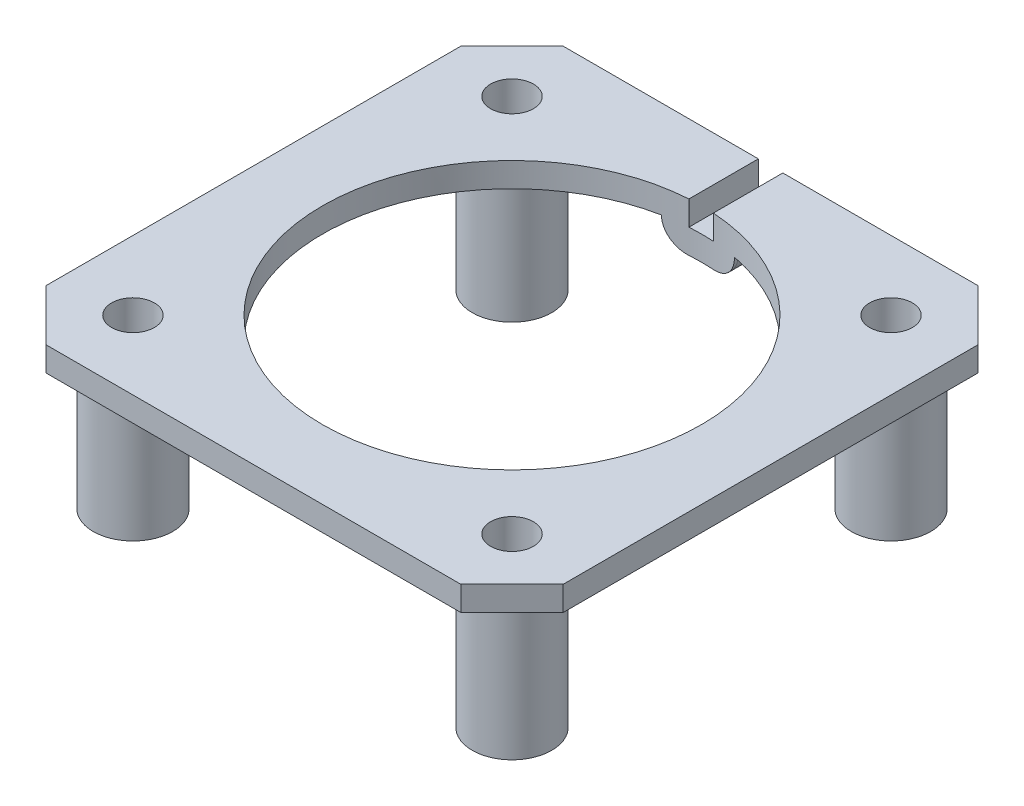
SolidWorks part; units mm, degrees
ref_plane "Front Plane" through (0, 0, 0) normal (0, 0, 1) x (1, 0, 0)
ref_plane "Top Plane" through (0, 0, 0) normal (0, 1, 0) x (1, 0, 0)
ref_plane "Right Plane" through (0, 0, 0) normal (1, 0, 0) x (0, 0, -1)
sketch "Sketch1" plane through (0, 0, 0) normal (0, 1, 0) x (1, 0, 0)
  circle A4 centre (-15.5, 15.5) radius 3.25
  dimension "D3" = 6.5
extrude "Boss-Extrude1" add sketch "Sketch1" along normal blind 13.7
mirror "Mirror2" about plane through (0, 0, 0) normal (1, 0, 0) of bodies 101
mirror "Mirror3" about plane through (0, 0, 0) normal (0, 0, 1) of bodies 101 102
sketch "Sketch2" plane through (0, 13.7, 0) normal (0, 1, 0) x (1, 0, 0)
  line L1 (-21.15, 21.15) -> (21.15, 21.15)
  line L2 (-21.15, 21.15) -> (-21.15, -21.15)
  line L3 (-21.15, -21.15) -> (21.15, -21.15)
  line L4 (21.15, 21.15) -> (21.15, -21.15)
  line L5 (-21.15, 21.15) -> (21.15, -21.15) construction
  line L6 (-21.15, -21.15) -> (21.15, 21.15) construction
  circle A0 centre (0, 0) radius 15.5
  dimension "D1" = 31
  dimension "D4" = 42.3
extrude "Boss-Extrude2" add sketch "Sketch2" against normal blind 2
sketch "Sketch3" plane through (0, 13.7, 0) normal (0, 1, 0) x (1, 0, 0)
  line L0 (-16.9631, 21.15) -> (-21.15, 16.9631)
  line L1 (21.15, 21.15) -> (-21.15, 21.15) construction
  line L2 (-21.15, 21.15) -> (-21.15, -21.15) construction
  line L3 (16.9631, -21.15) -> (21.15, -16.9631)
  line L4 (-21.15, -21.15) -> (21.15, -21.15) construction
  line L5 (21.15, -21.15) -> (21.15, 21.15) construction
  line L6 (-21.15, 16.9631) -> (-21.15, 21.15)
  line L7 (-21.15, 21.15) -> (-16.9631, 21.15)
  line L8 (21.15, -16.9631) -> (21.15, -21.15)
  line L9 (21.15, -21.15) -> (16.9631, -21.15)
  dimension "D1" = 45
  dimension "D2" = 53.9
extrude "Cut-Extrude1" cut sketch "Sketch3" against normal through all
mirror "Mirror4" about plane through (0, 0, 0) normal (0, 0, 1) of "Cut-Extrude1"
sketch "Sketch4" plane through (0, 0, 0) normal (0, -1, 0) x (1, 0, 0)
  circle A1 centre (15.5, -15.5) radius 3.25 construction
  circle A3 centre (15.5, -15.5) radius 1.75
  dimension "D1" = 3.5
extrude "Cut-Extrude2" cut sketch "Sketch4" against normal through all
mirror "Mirror5" about plane through (0, 0, 0) normal (1, 0, 0) of "Cut-Extrude2"
mirror "Mirror6" about plane through (0, 0, 0) normal (0, 0, 1) of "Mirror5"
sketch "Sketch6" plane through (0, 11.7, 0) normal (0, -1, 0) x (1, 0, 0)
  line L0 (0, -21.15) -> (0, -15.5) construction
  line L1 (16.9631, -21.15) -> (-16.9631, -21.15) construction
  line L2 (-3, -21.15) -> (-3, -15.5)
  line L3 (3, -21.15) -> (3, -15.5)
  line L4 (3, -21.15) -> (-3, -21.15)
  circle A0 centre (0, 0) radius 15.5 construction
  arc A2 (3, -15.5) -> (2.9859, -15.2097) centre (0, -15.5) ccw
  arc A3 (-2.9859, -15.2097) -> (2.9859, -15.2097) centre (0, 0) ccw
  arc A4 (-2.9859, -15.2097) -> (-3, -15.5) centre (0, -15.5) ccw
  point P7 (0, -18.325)
  dimension "D1" = 6
extrude "Boss-Extrude3" add sketch "Sketch6" along normal blind 2
sketch "Sketch7" plane through (0, 13.7, 0) normal (0, 1, 0) x (1, 0, 0)
  line L0 (0, 15.5) -> (0, 21.15) construction
  line L1 (16.9631, 21.15) -> (-16.9631, 21.15) construction
  line L2 (-1, 15.5) -> (-1, 21.15)
  line L3 (1, 15.5) -> (1, 21.15)
  circle A0 centre (0, 0) radius 15.5 construction
  arc A1 (-1, 15.5) -> (1, 15.5) centre (0, 15.5) ccw
  arc A2 (1, 21.15) -> (-1, 21.15) centre (0, 21.15) ccw
  point P6 (0, 18.325)
  dimension "D1" = 2
extrude "Cut-Extrude3" cut sketch "Sketch7" against normal blind 2
fillet "Fillet1" radius 2 4 edges at (2.9965, 9.7, -15.3547) (-2.9965, 9.7, -15.3547) (3, 9.7, -18.325) (-3, 9.7, -18.325)
